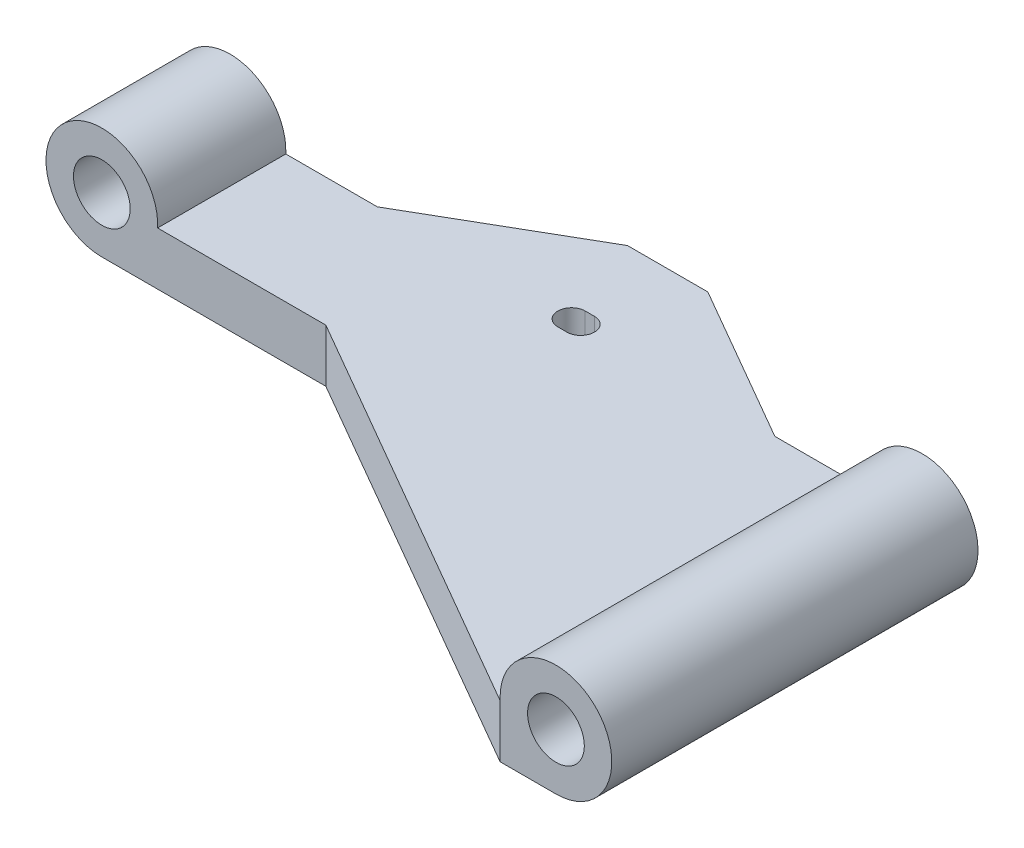
SolidWorks part; units mm, degrees
ref_plane "前视基准面" through (0, 0, 0) normal (0, 0, 1) x (1, 0, 0)
ref_plane "上视基准面" through (0, 0, 0) normal (0, 1, 0) x (1, 0, 0)
ref_plane "右视基准面" through (0, 0, 0) normal (1, 0, 0) x (0, 0, -1)
other "Configuration Table"
ref_plane "基准面1" through (0, 0, 70) normal (0, 0, 1) x (1, 0, 0)
sketch "草图2" plane through (0, 0, 70) normal (0, 0, 1) x (1, 0, 0)
  line L0 (0, 38.9897) -> (0, -8.3007) construction
  line L1 (-9.73, 15.6) -> (9.73, 15.6) construction
  line L2 (15.8539, 15.6) -> (-15.8539, 15.6)
  line L3 (-18.9, 12.705) -> (18.9, 12.705)
  circle A0 centre (-18.9, 15.755) radius 1.55
  circle A1 centre (-18.9, 15.755) radius 3.05
  circle A2 centre (18.9, 15.755) radius 3.05
  circle A3 centre (18.9, 15.755) radius 1.55
  dimension "D1" = 3.1
  dimension "D3" = 2.895
  dimension "D2" = 1.5
extrude "凸台-拉伸1" add sketch "草图2" against normal blind 25 contours A1 A0 | L0 L2 A1 L3 | L2 L0 L3 A2 | A2 A3 region at (8.2838, 14.1205, 70) region at (-8.2838, 14.1205, 70) region at (18.8247, 18.7178, 70) region at (-16.8583, 13.6067, 70)
sketch "草图3" [suppressed] plane through (0, 15.6, 0) normal (0, 1, 0) x (1, 0, 0)
  line L5 (21.95, -70) -> (21.95, -55) construction
  line L6 (21.95, -55) -> (-21.95, -55)
  line L7 (21.95, -55) -> (21.95, -63)
  line L8 (21.95, -63) -> (-21.95, -63)
  line L9 (-21.95, -55) -> (-21.95, -63)
  line L10 (-21.95, -55) -> (-21.95, -70) construction
  line L11 (15.8539, -70) -> (-15.8539, -70) construction
  line L12 (15.85, -63) -> (1.9936, -55)
  line L13 (15.85, -55) -> (15.85, -70) construction
  line L14 (-15.85, -63) -> (-1.9936, -55)
  line L15 (-15.85, -70) -> (-15.85, -55) construction
  line M8 (15.8539, -70) -> (15.8539, -55)
  line M9 (15.8539, -55) -> (-15.8539, -55)
  line M10 (-15.8539, -55) -> (-15.8539, -70)
  dimension "D1" = 7
  dimension "D2" = 30
  dimension "D3" = 30
extrude "切除-拉伸1" [suppressed] cut sketch "草图3" against normal through all both and the other way through all contours L8 L14 M9 M10 | L6 L9 L8 M10 | L12 L8 M8 M9 | L8 L7 L6 M8
sketch "草图4" plane through (0, 0, 70) normal (0, 0, 1) x (1, 0, 0)
  line L2 (-18.9, 12.705) -> (18.9, 12.705)
  line L3 (15.8539, 15.6) -> (-15.8539, 15.6)
  circle A0 centre (18.9, 15.755) radius 1.55 construction
  circle A1 centre (18.9, 15.755) radius 1.55
  arc A2 (-15.8539, 15.6) -> (-18.9, 12.705) centre (-18.9, 15.755) ccw
  arc A3 (18.9, 12.705) -> (15.8539, 15.6) centre (18.9, 15.755) ccw
  circle A5 centre (18.9, 15.755) radius 3.05
  dimension "D1" = 0
extrude "凸台-拉伸2" [suppressed] add sketch "草图4" along normal blind 13
sketch "草图5" [suppressed] plane through (0, 15.6, 0) normal (0, 1, 0) x (1, 0, 0)
  line L0 (2.85, -70) -> (15.85, -83)
  line L1 (15.8539, -70) -> (-15.8539, -70) construction
  line L3 (15.85, -63) -> (15.85, -83) construction
  line L4 (2.85, -70) -> (18.9, -70)
  line L5 (18.9, -70) -> (18.9, -83)
  line L6 (15.85, -83) -> (21.95, -83) construction
  line L7 (18.9, -83) -> (15.85, -83)
  line L11 (15.85, -63) -> (15.85, -83) construction
  line L12 (21.95, -83) -> (21.95, -63) construction
  dimension "D1" = 45
extrude "凸台-拉伸3" [suppressed] add sketch "草图5" against normal up to surface (2.895 mm away) up to face at (0, 12.705, 57.5)
sketch "草图6" [suppressed] plane through (0, 0, 83) normal (0, 0, 1) x (1, 0, 0)
  arc A0 (18.9, 14.205) -> (17.3578, 15.6) centre (18.9, 15.755) ccw construction
  circle A1 centre (18.9, 15.755) radius 1.55
extrude "切除-拉伸2" [suppressed] cut sketch "草图6" against normal through all
sketch "草图7" plane through (0, 15.6, 0) normal (0, 1, 0) x (1, 0, 0)
  line L0 (0, -53.0632) -> (0, -71.4882) construction
  line L1 (0.25, -50) -> (-0.25, -50) construction
  line L2 (0.25, -50.75) -> (-0.25, -50.75)
  line L3 (0.25, -49.25) -> (-0.25, -49.25)
  line L4 (15.8539, -45) -> (-15.8539, -45) construction
  arc A0 (0.25, -50.75) -> (0.25, -49.25) centre (0.25, -50) ccw
  arc A1 (-0.25, -49.25) -> (-0.25, -50.75) centre (-0.25, -50) ccw
  point P5 (0, -50)
  dimension "D1" = 5
  dimension "D2" = 1.5
  dimension "D3" = 0.5
extrude "切除-拉伸3" cut sketch "草图7" against normal through all
sketch "草图8" plane through (0, 12.705, 0) normal (0, -1, 0) x (1, 0, 0)
  circle A0 centre (0, 50) radius 1.6
  dimension "D1" = 3.2
extrude "切除-拉伸4" cut sketch "草图8" against normal blind 0.8
sketch "草图11" plane through (0, 15.6, 0) normal (0, 1, 0) x (1, 0, 0)
  line L0 (15.85, -70) -> (21.95, -70) construction
  line L1 (21.95, -45) -> (15.85, -45) construction
  line L2 (15.8539, -45) -> (15.8539, -70) construction
  line L3 (18.9, -70) -> (-18.9, -70) construction
  line L4 (-15.8539, -70) -> (15.8539, -70)
  line L5 (15.8539, -70) -> (15.8539, -45)
  line L6 (15.8539, -45) -> (-15.8539, -45)
  line L7 (-15.8539, -45) -> (-15.8539, -70)
  line L8 (-15.8539, -70) -> (15.8539, -70)
  line L9 (15.8539, -70) -> (15.8539, -45)
  line L10 (15.8539, -45) -> (-15.8539, -45)
  line L11 (-15.8539, -45) -> (-15.8539, -70)
  line L12 (-18.9, -45) -> (18.9, -45) construction
  line L13 (-21.95, -70) -> (-15.85, -70) construction
  line L14 (-15.8539, -70) -> (-15.8539, -45) construction
  line L15 (-15.85, -45) -> (-21.95, -45) construction
  line L16 (15.85, -70) -> (21.95, -70)
  line L17 (21.95, -45) -> (15.85, -45)
  line L18 (15.8539, -45) -> (15.8539, -70)
  line L19 (18.9, -70) -> (-18.9, -70)
  line L20 (-18.9, -45) -> (18.9, -45)
  line L21 (-21.95, -70) -> (-15.85, -70)
  line L22 (-15.8539, -70) -> (-15.8539, -45)
  line L23 (-15.85, -45) -> (-21.95, -45)
  line L24 (-6.6667, -57) -> (-15.8539, -57)
  line L25 (-15.8539, -57) -> (-21.95, -57)
  line L26 (-21.95, -57) -> (-21.95, -70)
  line L29 (-15.8539, -50) -> (-21.95, -50)
  line L30 (-21.95, -50) -> (-21.95, -45)
  line L31 (0, -40.5651) -> (0, -73.1573) construction
  line L32 (15.85, -70) -> (-6.6667, -57)
  line L33 (15.8539, -50) -> (21.95, -50)
  line L34 (21.95, -50) -> (21.95, -45)
  line L35 (-15.8539, -50) -> (-10.8539, -50)
  line L36 (-10.8539, -50) -> (-2.1937, -45)
  line L37 (2.1937, -45) -> (10.8539, -50)
  line L38 (10.8539, -50) -> (15.8539, -50)
  line M14 (-15.8539, -70) -> (15.8539, -70)
  line M16 (15.8539, -45) -> (-15.8539, -45)
  line M17 (-15.8539, -45) -> (-15.8539, -70)
  dimension "D2" = 5
  dimension "D3" = 7
  dimension "D4" = 30
  dimension "D5" = 30
  dimension "D6" = 30
  dimension "D7" = 5
  dimension "D8" = 5
  dimension "D1" = 0
extrude "切除-拉伸10" cut sketch "草图11" against normal through all both and the other way through all contours L33 L34 L17 L18 | L18 L10 M16 | L32 L31 M14 | L31 L32 L24 L22 L19 M14 | L25 L26 L21 L19 L22 | L30 L29 L20 L23 M17 | L20 M17 region at (-8.3057, 15.6, 63.8463) region at (-18.902, 15.6, 63.5) region at (5.2833, 15.6, 66.9497) region at (-18.902, 15.6, 47.5) region at (-10.8539, 15.6, 47.1132) region at (10.8539, 15.6, 47.1132) region at (18.902, 15.6, 47.5)
